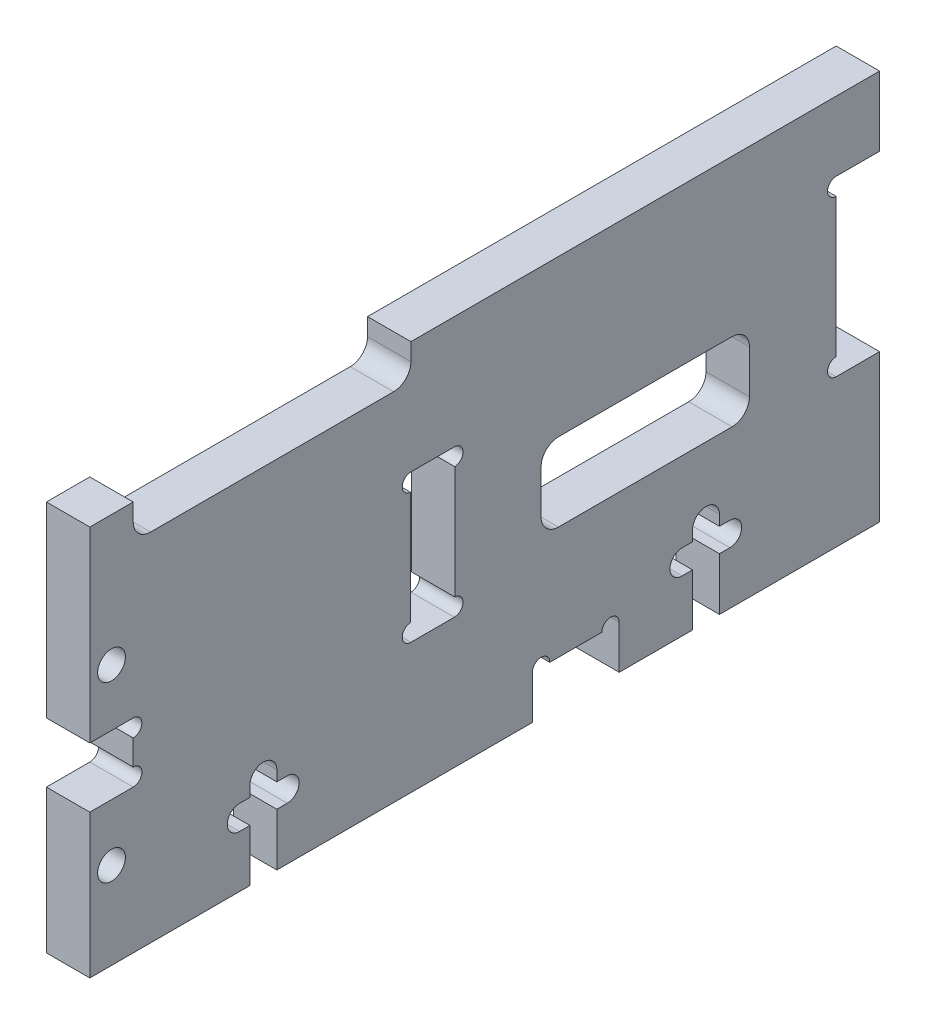
SolidWorks part; units mm, degrees
ref_plane "정면" through (0, 0, 0) normal (0, 0, 1) x (1, 0, 0)
ref_plane "윗면" through (0, 0, 0) normal (0, 1, 0) x (1, 0, 0)
ref_plane "우측면" through (0, 0, 0) normal (1, 0, 0) x (0, 0, -1)
sketch "스케치1" plane through (0, 0, 0) normal (1, 0, 0) x (0, 0, -1)
  line L1 (0, 0) -> (91, 0)
  line L2 (0, 0) -> (0, 45)
  line L3 (0, 45) -> (91, 45)
  line L4 (91, 0) -> (91, 45)
  dimension "D1" = 45
  dimension "D2" = 91
extrude "보스-돌출1" add sketch "스케치1" along normal blind 5
sketch "스케치2" plane through (5, 0, 0) normal (1, 0, 0) x (0, 0, -1)
  line L0 (0, 45) -> (0, 0) construction
  line L1 (0, 41) -> (5, 41)
  line L2 (0, 41) -> (0, 31)
  line L3 (0, 31) -> (5, 31)
  line L4 (5, 41) -> (5, 31)
  line L5 (91, 0) -> (91, 45) construction
  line L6 (0, 19) -> (5, 19)
  line L7 (0, 19) -> (0, 9)
  line L8 (0, 9) -> (5, 9)
  line L9 (5, 19) -> (5, 9)
  line L10 (37, 41) -> (42, 41)
  line L11 (37, 41) -> (37, 31)
  line L12 (37, 31) -> (42, 31)
  line L13 (42, 41) -> (42, 31)
  line L14 (37, 19) -> (42, 19)
  line L15 (37, 19) -> (37, 9)
  line L16 (37, 9) -> (42, 9)
  line L17 (42, 19) -> (42, 9)
  line L18 (86, 41) -> (91, 41)
  line L19 (86, 41) -> (86, 31)
  line L20 (86, 31) -> (91, 31)
  line L21 (91, 41) -> (91, 31)
  line L22 (5, 31) -> (37, 31) construction
  line L23 (86, 19) -> (91, 19)
  line L24 (86, 19) -> (86, 9)
  line L25 (86, 9) -> (91, 9)
  line L26 (91, 19) -> (91, 9)
  line L27 (37, 19) -> (37, 31) construction
  line L28 (5, 19) -> (5, 31) construction
  line L29 (37, 41) -> (5, 41) construction
  line L30 (42, 41) -> (86, 41) construction
  line L31 (86, 31) -> (86, 19) construction
  line L32 (42, 31) -> (42, 19) construction
  line L33 (42, 19) -> (86, 19) construction
  line L34 (86, 31) -> (42, 31) construction
  line L35 (42, 9) -> (86, 9) construction
  line L36 (37, 19) -> (5, 19) construction
  line L37 (5, 9) -> (37, 9) construction
  line L38 (91, 45) -> (0, 45) construction
  dimension "D1" = 5
  dimension "D2" = 5
  dimension "D3" = 5
  dimension "D4" = 10
  dimension "D5" = 10
  dimension "D6" = 12
  dimension "D7" = 4
  dimension "D8" = 32
extrude "컷-돌출1" [suppressed] cut sketch "스케치2" against normal blind 5
sketch "스케치3" [suppressed] plane through (5, 0, 0) normal (1, 0, 0) x (0, 0, -1)
  line L0 (91, 36) -> (86, 36) construction
  line L1 (86, 26) -> (91, 26) construction
  line L2 (91, 14) -> (86, 14) construction
  line L3 (86, 4) -> (91, 4) construction
  line L4 (42, 4) -> (42, 14) construction
  line L5 (37, 14) -> (37, 4) construction
  line L6 (37, 36) -> (37, 26) construction
  line L7 (42, 26) -> (42, 36) construction
  line L9 (5, 14) -> (0, 14) construction
  line L10 (0, 26) -> (5, 26) construction
  line L11 (5, 36) -> (0, 36) construction
  line L12 (0, 4) -> (5, 4) construction
  circle A0 centre (87, 36) radius 1
  circle A1 centre (87, 26) radius 1
  circle A2 centre (87, 14) radius 1
  circle A3 centre (87, 4) radius 1
  circle A4 centre (42, 13) radius 1
  circle A5 centre (37, 13) radius 1
  circle A6 centre (37, 27) radius 1
  circle A7 centre (42, 27) radius 1
  circle A8 centre (42, 35) radius 1
  circle A9 centre (37, 35) radius 1
  circle A10 centre (37, 5) radius 1
  circle A11 centre (42, 5) radius 1
  circle A12 centre (4, 14) radius 1
  circle A13 centre (4, 26) radius 1
  circle A14 centre (4, 36) radius 1
  circle A15 centre (4, 4) radius 1
  dimension "D1" = 2
extrude "컷-돌출2" [suppressed] cut sketch "스케치3" against normal blind 5
sketch "스케치7" plane through (5, 0, 0) normal (1, 0, 0) x (0, 0, -1)
  line L0 (86, 39) -> (86, 52) construction
  line L1 (52, 27) -> (76, 27)
  line L2 (52, 27) -> (52, 18)
  line L3 (52, 18) -> (76, 18)
  line L4 (76, 27) -> (76, 18)
  line L5 (42, 34) -> (42, 52) construction
  line L6 (91, 45) -> (0, 45) construction
  line L7 (0, 0) -> (91, 0) construction
  dimension "D1" = 10
  dimension "D2" = 10
  dimension "D3" = 18
  dimension "D4" = 18
extrude "컷-돌출3" cut sketch "스케치7" against normal blind 10
fillet "필렛1" radius 2 4 edges at (2.5, 18, -52) (2.5, 18, -76) (2.5, 27, -76) (2.5, 27, -52)
sketch "스케치8" plane through (5, 0, 0) normal (1, 0, 0) x (0, 0, -1)
  line L0 (91, 45) -> (0, 45) construction
  line L1 (5, 45) -> (37, 45)
  line L2 (5, 45) -> (5, 41)
  line L3 (5, 41) -> (37, 41)
  line L4 (37, 45) -> (37, 41)
  line L5 (5, 31.55) -> (5, 52) construction
  line L6 (37, 34) -> (37, 52) construction
  dimension "D1" = 4
extrude "컷-돌출4" cut sketch "스케치8" against normal blind 10
fillet "필렛2" radius 2 2 edges at (2.5, 41, -37) (2.5, 41, -5)
sketch "스케치9" plane through (0, 0, 0) normal (-1, 0, 0) x (0, 0, 1)
  line L1 (-42, 32) -> (-37, 32)
  line L2 (-42, 32) -> (-42, 15)
  line L3 (-42, 15) -> (-37, 15)
  line L4 (-37, 32) -> (-37, 15)
extrude "컷-돌출5" cut sketch "스케치9" against normal blind 5
sketch "스케치10" plane through (5, 0, 0) normal (1, 0, 0) x (0, 0, -1)
  line L0 (42, 32) -> (42, 15) construction
  line L1 (37, 15) -> (37, 32) construction
  circle A0 centre (42, 31) radius 1
  circle A1 centre (42, 16) radius 1
  circle A2 centre (37, 16) radius 1
  circle A3 centre (37, 31) radius 1
  dimension "D1" = 2
sketch "스케치14" plane through (5, 0, 0) normal (1, 0, 0) x (0, 0, -1)
  line L5 (2.5, 31.55) -> (2.5, 28.45) construction
  line L6 (5, 31.55) -> (0, 31.55) construction
  line L7 (5, 28.45) -> (0, 28.45) construction
  line L8 (2.5, 11.55) -> (2.5, 8.45) construction
  line L9 (5, 11.55) -> (0, 11.55) construction
  line L10 (5, 8.45) -> (0, 8.45) construction
  circle A0 centre (2.5, 10) radius 1.55
  circle A1 centre (2.5, 30) radius 1.55
extrude "컷-돌출9" cut sketch "스케치14" against normal blind 10
extrude "컷-돌출6" cut sketch "스케치10" against normal blind 10
sketch "스케치12" plane through (5, 0, 0) normal (1, 0, 0) x (0, 0, -1)
  line L1 (2.5, 30) -> (2.5, 10) construction
  line L4 (0, 45) -> (0, 0) construction
  line L5 (0, 0) -> (91, 0) construction
  circle A0 centre (2.5, 30) radius 1.6
  circle A1 centre (2.5, 10) radius 1.6
  dimension "D5" = 2.5
  dimension "D6" = 20
  dimension "D7" = 10
extrude "컷-돌출7" cut sketch "스케치12" against normal blind 10
sketch "스케치13" plane through (5, 0, 0) normal (1, 0, 0) x (0, 0, -1)
  line L0 (18.45, 0) -> (18.45, 6)
  line L1 (18.45, 0) -> (21.55, 0)
  line L2 (21.55, 0) -> (21.55, 6.0651)
  line L3 (18.45, 10) -> (21.55, 10) construction
  line L4 (21.55, 8.7999) -> (21.55, 10)
  line L5 (18.45, 6) -> (17.2502, 6)
  line L6 (17.2502, 6) -> (17.2325, 8.7999) construction
  line L7 (17.2325, 8.7999) -> (18.45, 8.7999)
  line L8 (21.55, 8.7999) -> (22.7498, 8.7999)
  line L9 (22.7498, 8.7999) -> (22.7498, 6.0651) construction
  line L10 (18.45, 8.7999) -> (18.45, 10)
  line L11 (22.7498, 6.0651) -> (21.55, 6.0651)
  line L12 (18.45, 6) -> (21.55, 6.0651) construction
  line L13 (18.45, 8.7999) -> (21.55, 8.7999) construction
  line L14 (21.55, 6.0651) -> (21.55, 8.7999) construction
  line L15 (18.45, 8.7999) -> (18.45, 6) construction
  line L16 (20, 10) -> (20, 16.1272) construction
  line L17 (0, 45) -> (0, 0) construction
  line L18 (72.55, 0) -> (72.55, 6.0651)
  line L19 (69.45, 10) -> (72.55, 10) construction
  line L20 (68.2502, 6) -> (68.2325, 8.7999) construction
  line L21 (72.55, 6.0651) -> (72.55, 8.7999) construction
  line L22 (69.45, 0) -> (72.55, 0)
  line L23 (68.2325, 8.7999) -> (69.45, 8.7999)
  line L24 (69.45, 0) -> (69.45, 6)
  line L25 (73.7498, 8.7999) -> (73.7498, 6.0651) construction
  line L26 (69.45, 6) -> (68.2502, 6)
  line L27 (69.45, 8.7999) -> (69.45, 6) construction
  line L28 (72.55, 8.7999) -> (72.55, 10)
  line L29 (69.45, 6) -> (72.55, 6.0651) construction
  line L30 (69.45, 8.7999) -> (72.55, 8.7999) construction
  line L31 (72.55, 8.7999) -> (73.7498, 8.7999)
  line L32 (69.45, 8.7999) -> (69.45, 10)
  line L33 (71, 10) -> (71, 16.1272) construction
  line L34 (73.7498, 6.0651) -> (72.55, 6.0651)
  line L35 (91, 0) -> (91, 45) construction
  arc A0 (17.2325, 8.7999) -> (17.2502, 6) centre (17.2414, 7.4) ccw
  arc A1 (22.7498, 6.0651) -> (22.7498, 8.7999) centre (22.7498, 7.4325) ccw
  arc A2 (21.55, 10) -> (18.45, 10) centre (20, 10) ccw
  arc A3 (72.55, 10) -> (69.45, 10) centre (71, 10) ccw
  arc A4 (68.2325, 8.7999) -> (68.2502, 6) centre (68.2414, 7.4) ccw
  arc A5 (73.7498, 6.0651) -> (73.7498, 8.7999) centre (73.7498, 7.4325) ccw
  dimension "D1" = 3.1
  dimension "D2" = 10
  dimension "D3" = 5.5
  dimension "D4" = 2.8
  dimension "D5" = 20
  dimension "D6" = 6
  dimension "D7" = 3.1
  dimension "D8" = 10
  dimension "D9" = 5.5
  dimension "D10" = 2.8
  dimension "D11" = 6
  dimension "D12" = 20
extrude "컷-돌출8" cut sketch "스케치13" against normal blind 10
sketch "스케치15" plane through (5, 0, 0) normal (1, 0, 0) x (0, 0, -1)
  line L0 (21.55, 0) -> (69.45, 0) construction
  line L1 (51, 5) -> (61, 5)
  line L2 (51, 5) -> (51, 0)
  line L3 (51, 0) -> (61, 0)
  line L4 (61, 5) -> (61, 0)
  line L5 (61, 5) -> (61, 0) construction
extrude "컷-돌출10" cut sketch "스케치15" against normal blind 10
sketch "스케치19" plane through (0, 0, 0) normal (-1, 0, 0) x (0, 0, 1)
  line L0 (0, 45) -> (0, 0) construction
  line L1 (-5, 23.45) -> (0, 23.45)
  line L2 (-5, 23.45) -> (-5, 16.55)
  line L3 (-5, 16.55) -> (0, 16.55)
  line L4 (0, 23.45) -> (0, 16.55)
  line L5 (-5, 16.55) -> (0, 16.55) construction
  line L6 (-86, 17) -> (-91, 17) construction
  line L7 (-86, 37) -> (-91, 37)
  line L8 (-86, 37) -> (-86, 17)
  line L9 (-86, 17) -> (-91, 17)
  line L10 (-91, 37) -> (-91, 17)
  line L11 (-91, 0) -> (-91, 45) construction
extrude "컷-돌출14" cut sketch "스케치19" against normal blind 5
sketch "스케치16" plane through (0, 0, 0) normal (-1, 0, 0) x (0, 0, 1)
  line L0 (-51, 5) -> (-61, 5) construction
  line L1 (-86, 17) -> (-86, 37) construction
  line L2 (-5, 23.45) -> (-5, 16.55) construction
  circle A0 centre (-60, 5) radius 1
  circle A1 centre (-52, 5) radius 1
  circle A2 centre (-86, 36) radius 1
  circle A3 centre (-86, 18) radius 1
  circle A4 centre (-5, 22.45) radius 1
  circle A5 centre (-5, 17.55) radius 1
  dimension "D1" = 2
extrude "컷-돌출11" cut sketch "스케치16" against normal blind 10
sketch "스케치20" plane through (5, 0, 0) normal (1, 0, 0) x (0, 0, -1)
  line L0 (42, 30) -> (42, 17) construction
  line L1 (36.95, 31.1977) -> (42.05, 31.1977)
  line L2 (36.95, 31.1977) -> (36.95, 16)
  line L3 (36.95, 16) -> (42.05, 16)
  line L4 (42.05, 31.1977) -> (42.05, 16)
  line L5 (37, 17) -> (37, 30) construction
  dimension "D1" = 0.05
  dimension "D2" = 0.05
extrude "컷-돌출15" cut sketch "스케치20" against normal blind 10
